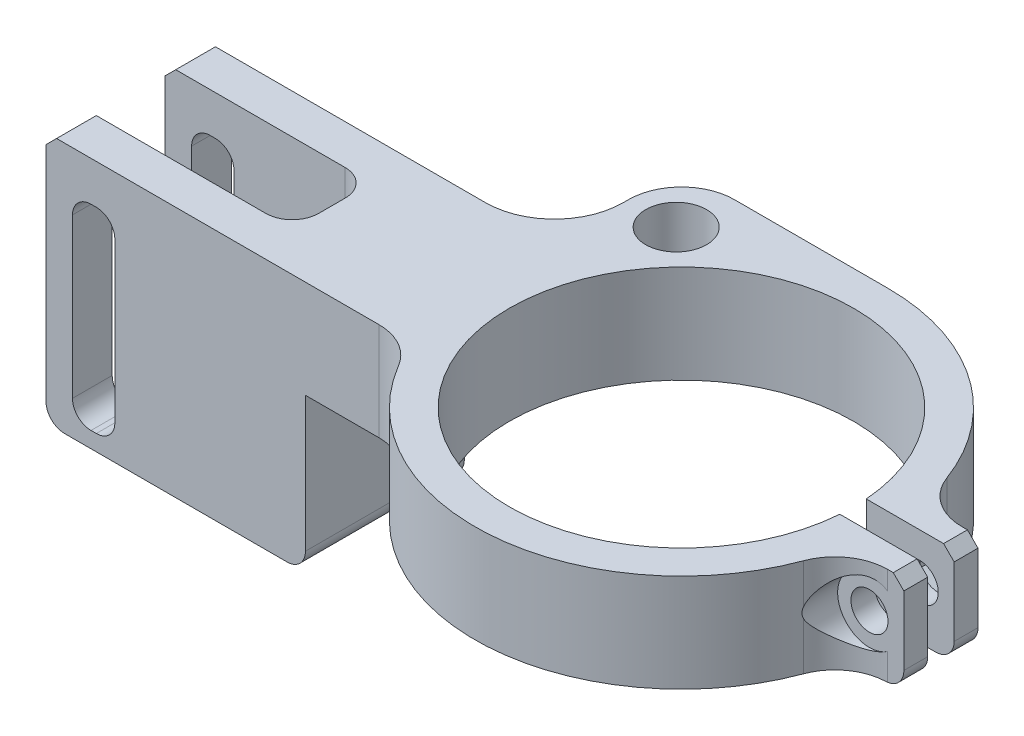
SolidWorks part; units mm, degrees
ref_plane "Front Plane" through (0, 0, 0) normal (0, 0, 1) x (1, 0, 0)
ref_plane "Top Plane" through (0, 0, 0) normal (0, 1, 0) x (1, 0, 0)
ref_plane "Right Plane" through (0, 0, 0) normal (1, 0, 0) x (0, 0, -1)
sketch "Sketch1" plane through (0, 0, 0) normal (0, 1, 0) x (1, 0, 0)
  line L7 (-29, 50) -> (0, 50)
  line L23 (-74, -4) -> (-46.1736, -4)
  line L26 (-74, 26) -> (-105, 26)
  line L27 (-105, 26) -> (-105, -4)
  line L28 (-105, -4) -> (-74, -4)
  line L30 (49, 13.5) -> (49, 18)
  line L31 (49, 18) -> (45.9565, 18)
  line L32 (49, 8.5) -> (49, 4)
  line L33 (49, 4) -> (45.9565, 4)
  line L34 (49, 13.5) -> (32.4037, 13.5)
  line L36 (49, 8.5) -> (32.4037, 8.5)
  line L37 (-39, 40) -> (-39, 39)
  line L38 (-52, 26) -> (-74, 26)
  line L39 (-33.3476, -9.2222) -> (-33.5946, -8.8148)
  line L40 (-42.1453, -4) -> (-46.1736, -4)
  arc A0 (32.4037, 13.5) -> (32.4037, 8.5) centre (0, 11) ccw
  circle A4 centre (-30, 40) radius 5.75
  arc A7 (-29, 50) -> (-39, 40) centre (-29, 40) ccw
  arc A8 (-33.3476, -9.2222) -> (36.5776, -2.5306) centre (0, 11) ccw
  arc A11 (36.5776, 24.5306) -> (0, 50) centre (0, 11) ccw
  arc A12 (36.5776, 24.5306) -> (45.9565, 18) centre (45.9565, 28) ccw
  arc A13 (36.5776, -2.5306) -> (45.9565, 4) centre (45.9565, -6) cw
  arc A14 (-39, 39) -> (-52, 26) centre (-52, 39) cw
  arc A15 (-42.1453, -4) -> (-33.5946, -8.8148) centre (-42.1453, -14) cw
  point P4 (55, -47)
  point P10 (-55, -47)
  point P30 (38.3667, 18)
  dimension "D1" = 10
  dimension "D2" = 13
  dimension "D3" = 10
  dimension "D4" = 10
  dimension "D5" = 10
extrude "Boss-Extrude1" add sketch "Sketch1" along normal blind 18.5
sketch "Sketch3" plane through (0, 0, 0) normal (0, -1, 0) x (1, 0, 0)
  line L0 (-55, -2.1421) -> (-55, -50) construction
  line L1 (-55, -2.1421) -> (-55, -26)
  line L2 (-105, 4) -> (-42.1453, 4) construction
  line L3 (-105, -26) -> (-105, 4) construction
  line L4 (-52, -26) -> (-105, -26) construction
  line L5 (-105, 4) -> (-55, 4)
  line L6 (-105, -26) -> (-105, 4)
  line L7 (-55, -26) -> (-105, -26)
  line L8 (-55, -2.1421) -> (-55, 4)
  line L9 (-56, -2.1421) -> (-56, -26)
  line L10 (-56, -2.1421) -> (-56, 4)
  line M2 (-105, 4) -> (-105, -26)
  line M3 (-105, -26) -> (-52, -26)
  dimension "D1" = 1
extrude "Boss-Extrude2" add sketch "Sketch3" along normal blind 29 contours L9 L10 L5 M2 M3
sketch "Sketch5" plane through (0, -29, 0) normal (0, -1, 0) x (-1, 0, 0)
  line L1 (66, 3.5) -> (66, 18.5)
  line L2 (105, 11) -> (105, 18.5)
  line L3 (105, -4) -> (105, 26) construction
  line L5 (105, 18.5) -> (66, 18.5)
  line L8 (66, 3.5) -> (105, 3.5)
  line L9 (105, 3.5) -> (105, 11)
extrude "Cut-Extrude1" cut sketch "Sketch5" against normal through all
sketch "Sketch6" plane through (0, 0, 4) normal (0, 0, 1) x (1, 0, 0)
  line L2 (-100, 11) -> (-100, -26)
  line L7 (-92, -26) -> (-100, -26)
  line L8 (-100, 11) -> (-92, 11)
  line L10 (-92, -5.5) -> (-92, -26)
  line L11 (-92, -26) -> (-92, 11)
  point P0 (-78, 19)
  point P2 (-75, 19)
  point P3 (-75, -20)
  point P4 (-56, -17)
  point P5 (-46.1736, 19)
  point P7 (-78, -17)
extrude "Cut-Extrude2" cut sketch "Sketch6" against normal through all contours L10 L11 L8 L2 L7
fillet "Fillet1" radius 3.5 11 edges at (-100, 11, -22.25) (-92, 11, -22.25) (-100, -26, -22.25) (-92, -26, -22.25) (-100, 11, 0.25) (-92, 11, 0.25) (-92, -26, 0.25) (-100, -26, 0.25) (-105, -29, 0.25) (-105, -29, -22.25) (-56, -29, -11)
chamfer "Chamfer1" distance 2 angle 45 1 edges at (-105, 18.5, 0.25)
sketch "Sketch7" plane through (0, 0, -4) normal (0, 0, 1) x (1, 0, 0)
  circle A0 centre (42.5, 10) radius 3.5
extrude "Cut-Extrude3" cut sketch "Sketch7" against normal through all and the other way through all
sketch "Sketch8" plane through (0, 0, -18) normal (0, 0, -1) x (-1, 0, 0)
  line L1 (-42.5, 16.0622) -> (-47.75, 13.0311)
  line L2 (-47.75, 13.0311) -> (-47.75, 6.9689)
  line L3 (-47.75, 6.9689) -> (-42.5, 3.9378)
  line L4 (-42.5, 3.9378) -> (-37.25, 6.9689)
  line L5 (-37.25, 6.9689) -> (-37.25, 13.0311)
  line L6 (-37.25, 13.0311) -> (-42.5, 16.0622)
  circle A0 centre (-42.5, 10) radius 5.25 construction
extrude "Cut-Extrude4" cut sketch "Sketch8" along normal blind 10 and the other way blind 1
sketch "Sketch9" plane through (0, 0, -4) normal (0, 0, 1) x (1, 0, 0)
  circle A0 centre (42.5, 10) radius 6
extrude "Cut-Extrude5" cut sketch "Sketch9" along normal blind 10
fillet "Fillet3" radius 3.5 2 edges at (49, 0, -15.75) (49, 0, -6.25)
chamfer "Chamfer2" distance 2 angle 45 2 edges at (49, 18.5, -6.25) (49, 18.5, -15.75)
fillet "Fillet4" radius 5 2 edges at (-66, -5.25, -3.5) (-66, -5.25, -18.5)
